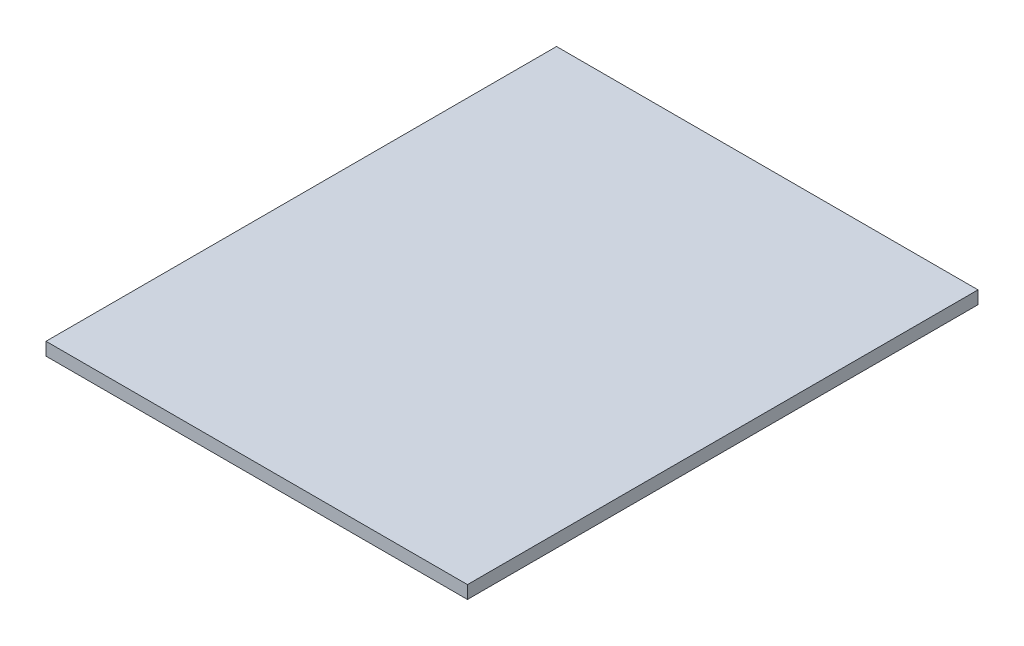
SolidWorks part; units mm, degrees
ref_plane "前视基准面" through (0, 0, 0) normal (0, 0, 1) x (1, 0, 0)
ref_plane "上视基准面" through (0, 0, 0) normal (0, 1, 0) x (1, 0, 0)
ref_plane "右视基准面" through (0, 0, 0) normal (1, 0, 0) x (0, 0, -1)
sketch "草图1" plane through (0, 0, 0) normal (0, 1, 0) x (1, 0, 0)
  line L1 (-16.3286, 19.7795) -> (16.3286, 19.7795)
  line L2 (-16.3286, 19.7795) -> (-16.3286, -19.7795)
  line L3 (-16.3286, -19.7795) -> (16.3286, -19.7795)
  line L4 (16.3286, 19.7795) -> (16.3286, -19.7795)
  line L5 (-16.3286, 19.7795) -> (16.3286, -19.7795) construction
  line L6 (-16.3286, -19.7795) -> (16.3286, 19.7795) construction
  point P0 (0, 0)
extrude "凸台-拉伸1" add sketch "草图1" along normal blind 1
